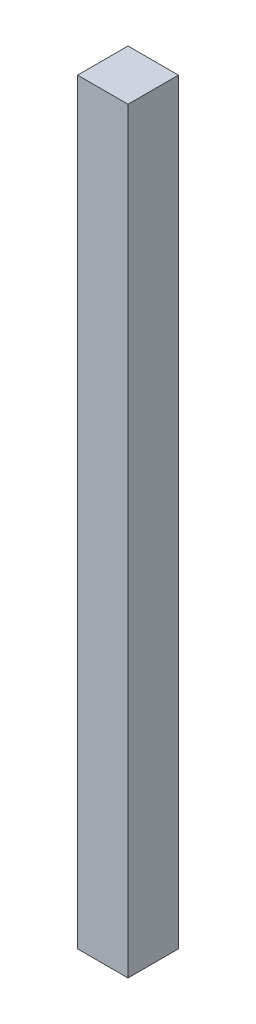
SolidWorks part; units mm, degrees
ref_plane "Front Plane" through (0, 0, 0) normal (0, 0, 1) x (1, 0, 0)
ref_plane "Top Plane" through (0, 0, 0) normal (0, 1, 0) x (1, 0, 0)
ref_plane "Right Plane" through (0, 0, 0) normal (1, 0, 0) x (0, 0, -1)
sketch "Sketch1" plane through (0, 0, 0) normal (0, 1, 0) x (1, 0, 0)
  line L1 (0, 0) -> (10, 0)
  line L2 (0, 0) -> (0, 10)
  line L3 (0, 10) -> (10, 10)
  line L4 (10, 0) -> (10, 10)
  dimension "D1" = 10
  dimension "D2" = 10
extrude "Boss-Extrude1" add sketch "Sketch1" along normal blind 150
